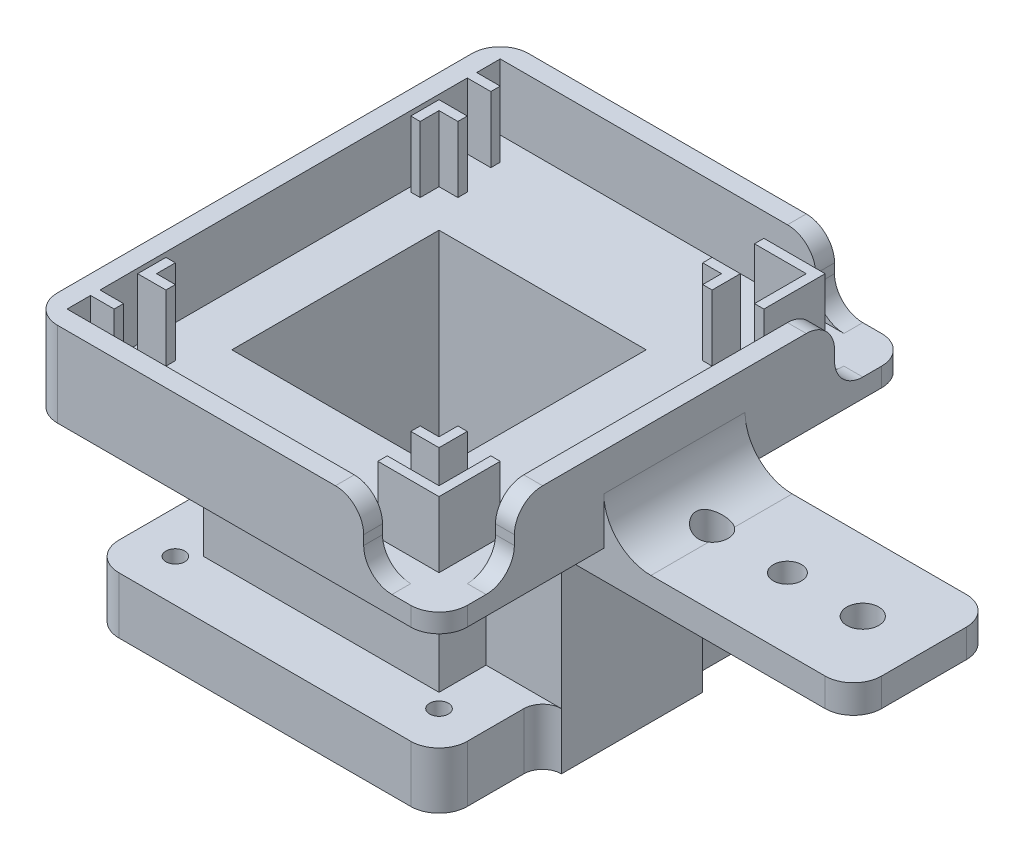
SolidWorks part; units mm, degrees
ref_plane "前视基准面" through (0, 0, 0) normal (0, 0, 1) x (1, 0, 0)
ref_plane "上视基准面" through (0, 0, 0) normal (0, 1, 0) x (1, 0, 0)
ref_plane "右视基准面" through (0, 0, 0) normal (1, 0, 0) x (0, 0, -1)
sketch "草图2" plane through (0, 0, 0) normal (0, 1, 0) x (1, 0, 0)
  line L1 (18.5, -18.5) -> (-18.5, -18.5)
  line L2 (18.5, -18.5) -> (18.5, 18.5)
  line L3 (18.5, 18.5) -> (-18.5, 18.5)
  line L4 (-18.5, -18.5) -> (-18.5, 18.5)
  line L5 (18.5, -18.5) -> (-18.5, 18.5) construction
  line L6 (18.5, 18.5) -> (-18.5, -18.5) construction
  point P0 (0, 0)
  dimension "D1" = 37
  dimension "D2" = 37
extrude "凸台-拉伸1" add sketch "草图2" along normal blind 23
sketch "草图3" plane through (0, 0, 0) normal (0, -1, 0) x (1, 0, 0)
  line L1 (11, -11) -> (-11, -11)
  line L2 (11, -11) -> (11, 11)
  line L3 (11, 11) -> (-11, 11)
  line L4 (-11, -11) -> (-11, 11)
  line L5 (11, -11) -> (-11, 11) construction
  line L6 (11, 11) -> (-11, -11) construction
  point P1 (0, 0)
  dimension "D1" = 22
  dimension "D2" = 22
extrude "切除-拉伸1" cut sketch "草图3" against normal blind 23
sketch3d "3D草图1" plane through (0, 0, 0) normal (0, 0, 1) x (1, 0, 0)
  dimension "D1" = 6
sketch "草图19" plane through (0, 6, 0) normal (0, -1, 0) x (-1, 0, 0)
  line L1 (-12.5, -12.5) -> (12.5, -12.5)
  line L2 (-12.5, -12.5) -> (-12.5, 12.5)
  line L3 (-12.5, 12.5) -> (12.5, 12.5)
  line L4 (12.5, -12.5) -> (12.5, 12.5)
  line L5 (-12.5, -12.5) -> (12.5, 12.5) construction
  line L6 (-12.5, 12.5) -> (12.5, -12.5) construction
  point P0 (0, 0)
  dimension "D1" = 25
  dimension "D2" = 25
extrude "切除-拉伸17" cut sketch "草图19" against normal blind 17 flip side to cut
sketch "草图4" plane through (0, 23, 0) normal (0, 1, 0) x (1, 0, 0)
  line L1 (25, 25) -> (-25, 25)
  line L2 (25, 25) -> (25, -25)
  line L3 (25, -25) -> (-25, -25)
  line L4 (-25, 25) -> (-25, -25)
  line L5 (25, 25) -> (-25, -25) construction
  line L6 (25, -25) -> (-25, 25) construction
  point P0 (0, 0)
  dimension "D1" = 50
  dimension "D2" = 50
extrude "凸台-拉伸2" add sketch "草图4" along normal blind 9
sketch "草图5" plane through (0, 32, 0) normal (0, 1, 0) x (1, 0, 0)
  line L1 (23, 23) -> (-23, 23)
  line L2 (23, 23) -> (23, -23)
  line L3 (23, -23) -> (-23, -23)
  line L4 (-23, 23) -> (-23, -23)
  line L5 (23, 23) -> (-23, -23) construction
  line L6 (23, -23) -> (-23, 23) construction
  point P0 (0, 0)
  dimension "D1" = 46
  dimension "D2" = 46
extrude "切除-拉伸3" cut sketch "草图5" against normal blind 7
sketch "草图12" plane through (0, 25, 0) normal (0, 1, 0) x (1, 0, 0)
  line L0 (-25, 25) -> (-25, -25) construction
  line L1 (-17, -17) -> (-25, -17)
  line L2 (-17, -17) -> (-17, -25)
  line L3 (-17, -25) -> (-25, -25)
  line L4 (-25, -17) -> (-25, -25)
  line L5 (-25, -25) -> (25, -25) construction
  line L6 (-17, 17) -> (-25, 17)
  line L7 (-17, 17) -> (-17, 25)
  line L8 (-17, 25) -> (-25, 25)
  line L9 (-25, 17) -> (-25, 25)
  line L10 (17, 17) -> (17, 25)
  line L11 (17, 17) -> (25, 17)
  line L12 (25, 17) -> (25, 25)
  line L13 (17, 25) -> (25, 25)
  line L14 (17, -17) -> (25, -17)
  line L15 (17, -17) -> (17, -25)
  line L16 (17, -25) -> (25, -25)
  line L17 (25, -17) -> (25, -25)
  dimension "D1" = 0
  dimension "D2" = 0
  dimension "D3" = 8
  dimension "D4" = 8
  dimension "D5" = 4
extrude "切除-拉伸14" cut sketch "草图12" along normal blind 14
sketch "草图6" plane through (0, 25, 0) normal (0, 1, 0) x (1, 0, 0)
  line L1 (11, 11) -> (-11, 11)
  line L2 (11, 11) -> (11, -11)
  line L3 (11, -11) -> (-11, -11)
  line L4 (-11, 11) -> (-11, -11)
  line L5 (11, 11) -> (-11, -11) construction
  line L6 (11, -11) -> (-11, 11) construction
  point P0 (0, 0)
  dimension "D1" = 22
  dimension "D2" = 22
extrude "切除-拉伸4" cut sketch "草图6" against normal blind 2
sketch "草图11" plane through (0, 0, 0) normal (0, -1, 0) x (1, 0, 0)
  line L0 (18.5, 18.5) -> (18.5, -18.5) construction
  line L1 (-18.5, 18.5) -> (18.5, 18.5) construction
  circle A0 centre (14, 14) radius 1
  circle A1 centre (14, -14) radius 1
  circle A2 centre (-14, -14) radius 1
  circle A3 centre (-14, 14) radius 1
  dimension "D1" = 4.5
  dimension "D3" = 2
  dimension "D2" = 4.5
  dimension "D4" = 4
extrude "切除-拉伸7" cut sketch "草图11" against normal blind 8
sketch "草图13" plane through (0, 25, 0) normal (0, 1, 0) x (1, 0, 0)
  line L1 (-20.5, 20.5) -> (20.5, 20.5)
  line L2 (-20.5, 20.5) -> (-20.5, -20.5)
  line L3 (-20.5, -20.5) -> (20.5, -20.5)
  line L4 (20.5, 20.5) -> (20.5, -20.5)
  line L5 (-20.5, 20.5) -> (20.5, -20.5) construction
  line L6 (-20.5, -20.5) -> (20.5, 20.5) construction
  line L7 (-19.5, 19.5) -> (19.5, 19.5)
  line L8 (-19.5, 19.5) -> (-19.5, -19.5)
  line L9 (-19.5, -19.5) -> (19.5, -19.5)
  line L10 (19.5, 19.5) -> (19.5, -19.5)
  line L11 (-19.5, 19.5) -> (19.5, -19.5) construction
  line L12 (-19.5, -19.5) -> (19.5, 19.5) construction
  point P0 (0, 0)
  point P6 (0, 0)
  dimension "D1" = 41
  dimension "D2" = 41
  dimension "D3" = 39
  dimension "D4" = 39
extrude "凸台-拉伸3" add sketch "草图13" along normal blind 7
sketch "草图17" plane through (0, 25, 0) normal (0, 1, 0) x (1, 0, 0)
  line L1 (15, -15) -> (-15, -15)
  line L2 (15, -15) -> (15, 15)
  line L3 (15, 15) -> (-15, 15)
  line L4 (-15, -15) -> (-15, 15)
  line L5 (15, -15) -> (-15, 15) construction
  line L6 (15, 15) -> (-15, -15) construction
  line L7 (16, -16) -> (-16, -16)
  line L8 (16, -16) -> (16, 16)
  line L9 (16, 16) -> (-16, 16)
  line L10 (-16, -16) -> (-16, 16)
  line L11 (16, -16) -> (-16, 16) construction
  line L12 (16, 16) -> (-16, -16) construction
  point P0 (0, 0)
  point P6 (0, 0)
  dimension "D1" = 30
  dimension "D2" = 30
  dimension "D3" = 32
  dimension "D4" = 32
extrude "凸台-拉伸4" add sketch "草图17" along normal blind 7
sketch "草图15" plane through (0, 25, 0) normal (0, 1, 0) x (1, 0, 0)
  line L0 (-14, -19.5) -> (-14, -20.5)
  line L1 (19.5, 14) -> (20.5, 14)
  line L2 (19.5, 14) -> (19.5, -14)
  line L3 (19.5, -14) -> (20.5, -14)
  line L4 (20.5, 14) -> (20.5, -14)
  line L5 (19.5, 14) -> (20.5, -14) construction
  line L6 (19.5, -14) -> (20.5, 14) construction
  line L7 (20.5, -20.5) -> (20.5, 20.5) construction
  line L8 (14, -20.5) -> (-14, -20.5)
  line L9 (19.5, -19.5) -> (19.5, 19.5) construction
  line L10 (14, -19.5) -> (-14, -19.5)
  line L11 (14, -19.5) -> (14, -20.5)
  line L12 (-19.5, 14) -> (-20.5, 14)
  line L13 (-20.5, -14) -> (-20.5, 14)
  line L14 (-19.5, -14) -> (-19.5, 14)
  line L15 (-19.5, -14) -> (-20.5, -14)
  line L16 (14, 19.5) -> (14, 20.5)
  line L17 (-14, 20.5) -> (14, 20.5)
  line L18 (-14, 19.5) -> (14, 19.5)
  line L19 (-14, 19.5) -> (-14, 20.5)
  point P0 (20, 0)
  point P5 (20.5, 0)
  point P6 (19.5, 0)
  point P11 (19.5, 0)
  dimension "D1" = 0
  dimension "D2" = 1
  dimension "D3" = 0
  dimension "D4" = 28
  dimension "D5" = 4
extrude "切除-拉伸15" cut sketch "草图15" along normal blind 7
sketch "草图18" plane through (0, 25, 0) normal (0, 1, 0) x (1, 0, 0)
  line L0 (15, -15) -> (15, 15) construction
  line L1 (16, -13) -> (15, -13)
  line L2 (16, -13) -> (16, 13)
  line L3 (16, 13) -> (15, 13)
  line L4 (15, -13) -> (15, 13)
  line L5 (16, -13) -> (15, 13) construction
  line L6 (16, 13) -> (15, -13) construction
  line L7 (16, -16) -> (16, 16) construction
  line L32 (-13, -16) -> (13, -16)
  line L33 (13, -16) -> (13, -15)
  line L34 (-13, -15) -> (13, -15)
  line L35 (-13, -16) -> (-13, -15)
  line L36 (-16, 13) -> (-16, -13)
  line L37 (-16, -13) -> (-15, -13)
  line L38 (-15, 13) -> (-15, -13)
  line L39 (-16, 13) -> (-15, 13)
  line L40 (13, 16) -> (-13, 16)
  line L41 (-13, 16) -> (-13, 15)
  line L42 (13, 15) -> (-13, 15)
  line L43 (13, 16) -> (13, 15)
  line L44 (0, 0) -> (15, -13) construction
  point P0 (15.5, 0)
  point P7 (16, 0)
  point P10 (16, 0)
  dimension "D1" = 0
  dimension "D2" = 1
  dimension "D3" = 0
  dimension "D4" = 26
  dimension "D5" = 4
  dimension "D6" = 19.8494
extrude "切除-拉伸16" cut sketch "草图18" along normal blind 7
sketch "草图20" plane through (0, 0, 0) normal (0, -1, 0) x (1, 0, 0)
  line L0 (-11, -11) -> (11, -11) construction
  line L1 (11, 0) -> (14, 0)
  line L2 (11, 0) -> (11, -10.5)
  line L3 (11, -10.5) -> (14, -10.5)
  line L4 (14, 0) -> (14, -10.5)
  line L5 (11, 0) -> (14, -10.5) construction
  line L6 (11, -10.5) -> (14, 0) construction
  line L7 (11, -11) -> (11, 11) construction
  point P0 (12.5, -5.25)
  dimension "D1" = 0.5
  dimension "D2" = 0
  dimension "D3" = 3
  dimension "D4" = 10.5
extrude "切除-拉伸18" cut sketch "草图20" against normal blind 3.5
sketch "草图21" plane through (0, 0, 0) normal (0, -1, 0) x (1, 0, 0)
  line L0 (-11, -11) -> (11, -11) construction
  line L1 (-11, -7) -> (-15.5, -7)
  line L2 (-11, -7) -> (-11, 3)
  line L3 (-11, 3) -> (-15.5, 3)
  line L4 (-15.5, -7) -> (-15.5, 3)
  line L5 (-11, -7) -> (-15.5, 3) construction
  line L6 (-11, 3) -> (-15.5, -7) construction
  line L7 (-11, 11) -> (-11, -11) construction
  point P0 (-13.25, -2)
  dimension "D1" = 4
  dimension "D2" = 10
  dimension "D3" = 0
  dimension "D4" = 4.5
extrude "切除-拉伸19" cut sketch "草图21" against normal blind 1
sketch "草图22" plane through (0, 0, 0) normal (0, -1, 0) x (1, 0, 0)
  line L1 (-2.5, -11) -> (2.5, -11)
  line L2 (-2.5, -11) -> (-2.5, -12)
  line L3 (-2.5, -12) -> (2.5, -12)
  line L4 (2.5, -11) -> (2.5, -12)
  line L5 (-2.5, -11) -> (2.5, -12) construction
  line L6 (-2.5, -12) -> (2.5, -11) construction
  line L7 (-11, -11) -> (11, -11) construction
  line L11 (0, 0) -> (7.3651, 0) construction
  line L13 (-2.5, 12) -> (2.5, 12)
  line L14 (2.5, 11) -> (2.5, 12)
  line L15 (-2.5, 11) -> (2.5, 11)
  line L16 (-2.5, 11) -> (-2.5, 12)
  point P0 (0, -11.5)
  point P7 (0, -11)
  point P8 (0, -11)
  point P9 (-2.5, -11.5)
  dimension "D1" = 1
  dimension "D2" = 0
  dimension "D3" = 0
  dimension "D4" = 5
extrude "切除-拉伸21" cut sketch "草图22" against normal blind 7
sketch "草图24" plane through (0, 0, 0) normal (0, -1, 0) x (1, 0, 0)
  line L0 (-11, -11) -> (-2.5, -11) construction
  line L1 (-1.5, -11) -> (-7.5, -11)
  line L2 (-1.5, -11) -> (-1.5, -15.5)
  line L3 (-1.5, -15.5) -> (-7.5, -15.5)
  line L4 (-7.5, -11) -> (-7.5, -15.5)
  line L5 (-1.5, -11) -> (-7.5, -15.5) construction
  line L6 (-1.5, -15.5) -> (-7.5, -11) construction
  line L7 (-11, -7) -> (-11, -11) construction
  point P0 (-4.5, -13.25)
  dimension "D1" = 0
  dimension "D2" = 3.5
  dimension "D3" = 4.5
  dimension "D4" = 6
extrude "切除-拉伸22" cut sketch "草图24" against normal blind 1
sketch "草图25" plane through (0, 6, 0) normal (0, 1, 0) x (1, 0, 0)
  line L0 (18.5, 18.5) -> (18.5, -18.5) construction
  line L1 (18.5, 7.5) -> (12.5, 7.5)
  line L2 (18.5, 7.5) -> (18.5, -7.5)
  line L3 (18.5, -7.5) -> (12.5, -7.5)
  line L4 (12.5, 7.5) -> (12.5, -7.5)
  line L5 (18.5, 7.5) -> (12.5, -7.5) construction
  line L6 (18.5, -7.5) -> (12.5, 7.5) construction
  line L7 (12.5, 12.5) -> (12.5, -12.5) construction
  point P0 (15.5, 0)
  point P9 (15.5, -7.5)
  point P10 (18.5, 0)
  point P11 (18.5, 0)
  dimension "D1" = 0
  dimension "D2" = 0
  dimension "D3" = 15
  dimension "D4" = 0
extrude "凸台-拉伸5" add sketch "草图25" along normal blind 17
sketch "草图26" plane through (18.5, 0, 0) normal (1, 0, 0) x (0, 0, -1)
  line L0 (-7.5, 23) -> (7.5, 23) construction
  line L1 (7.5, 20) -> (-7.5, 20)
  line L2 (7.5, 20) -> (7.5, 23)
  line L3 (7.5, 23) -> (-7.5, 23)
  line L4 (-7.5, 20) -> (-7.5, 23)
  line L5 (7.5, 20) -> (-7.5, 23) construction
  line L6 (7.5, 23) -> (-7.5, 20) construction
  line L7 (7.5, 23) -> (7.5, 6) construction
  line L8 (-7.5, 23) -> (-7.5, 6) construction
  point P0 (0, 21.5)
  dimension "D1" = 0
  dimension "D2" = 0
  dimension "D3" = 0
  dimension "D4" = 3
extrude "凸台-拉伸6" add sketch "草图26" along normal blind 33
sketch "草图28" plane through (0, 23, 0) normal (0, -1, 0) x (1, 0, 0)
  line L0 (-25, 25) -> (25, 25) construction
  line L1 (-25, -25) -> (-18.5, -25)
  line L2 (-25, -25) -> (-25, 25)
  line L3 (-25, 25) -> (-18.5, 25)
  line L4 (-18.5, -25) -> (-18.5, 25)
  dimension "D1" = 0
  dimension "D2" = 6.5
extrude "切除-拉伸27" cut sketch "草图28" against normal blind 13
sketch "草图32" plane through (0, 23, 0) normal (0, -1, 0) x (1, 0, 0)
  line L0 (-18.5, 25) -> (25, 25) construction
  line L1 (-18.5, -25) -> (-16.5, -25)
  line L2 (-18.5, -25) -> (-18.5, 25)
  line L3 (-18.5, 25) -> (-16.5, 25)
  line L4 (-16.5, -25) -> (-16.5, 25)
  dimension "D1" = 2
extrude "凸台-拉伸9" add sketch "草图32" against normal blind 9
fillet "圆角5" radius 3 1 edges at (25, 24, -25) type face fillet first side face at (25, 25.6, 0) second side face at (7.8333, 26.6667, -25)
fillet "圆角6" radius 3 1 edges at (25, 24, 25) type face fillet first side face at (7.8333, 26.6667, 25) second side face at (25, 25.6, 0.6)
fillet "圆角7" radius 3 1 edges at (-18.5, 27.5, -25) type face fillet first side face at (-18.5, 27.5, 0) second side face at (6.8333, 26.6667, -25)
fillet "圆角8" radius 3 1 edges at (-18.5, 27.5, 25) type face fillet first side face at (-18.5, 27.5, 1.5) second side face at (6.8333, 26.6667, 25)
fillet "圆角9" radius 3 1 edges at (17, 32, -24) type face fillet first side face at (-8.6801, 32, 0) second side face at (17, 28.5, -24)
fillet "圆角10" radius 3 1 edges at (17, 25, -24) type face fillet first side face at (-14.6667, 25, 14.6667) second side face at (17, 27, -24)
fillet "圆角11" radius 3 1 edges at (24, 32, -17) type face fillet first side face at (24, 28.5, -17) second side face at (24, 32, 0)
fillet "圆角12" radius 3 1 edges at (24, 25, -17) type face fillet first side face at (24, 27, -17) second side face at (-14.6667, 25, 14.6667)
fillet "圆角13" radius 3 1 edges at (17, 32, 24) type face fillet first side face at (-9.0135, 32, 0) second side face at (17, 28.5, 24)
fillet "圆角14" radius 3 1 edges at (17, 25, 24) type face fillet first side face at (17, 27, 24) second side face at (-14.6667, 25, 14.6667)
fillet "圆角15" radius 3 1 edges at (24, 32, 17) type face fillet first side face at (24, 32, 1.5) second side face at (24, 28.5, 17)
fillet "圆角16" radius 3 1 edges at (24, 25, 17) type face fillet first side face at (24, 27, 17) second side face at (-14.6667, 25, 14.6667)
fillet "圆角17" radius 5 1 edges at (25, 23, 0) type face fillet first side face at (25, 26.4286, 0) second side face at (38.25, 23, 0)
fillet "圆角19" radius 3 1 edges at (-18.5, 3, -18.5) type face fillet first side face at (-18.5, 3, 0) second side face at (0, 3, -18.5)
fillet "圆角20" radius 3 1 edges at (-18.5, 3, 18.5) type face fillet first side face at (-18.5, 3, 1.5) second side face at (0, 3, 18.5)
fillet "圆角21" radius 3 1 edges at (18.5, 3, 18.5) type face fillet first side face at (18.5, 8, 0) second side face at (1.5, 3, 18.5)
fillet "圆角22" radius 3 1 edges at (18.5, 3, -18.5) type face fillet first side face at (18.5, 8, -0.75) second side face at (1.5, 3, -18.5)
sketch "草图34" plane through (18.5, 0, 0) normal (1, 0, 0) x (0, 0, -1)
  line L0 (7.5, 20) -> (7.5, 6) construction
  line L1 (-7.5, 20) -> (7.5, 20)
  line L2 (-7.5, 20) -> (-7.5, 0)
  line L3 (-7.5, 0) -> (7.5, 0)
  line L4 (7.5, 20) -> (7.5, 0)
  dimension "D1" = 20
extrude "凸台-拉伸10" add sketch "草图34" along normal blind 2
sketch "草图33" plane through (0, 20, 0) normal (0, -1, 0) x (1, 0, 0)
  line L0 (18.5, 7.5) -> (18.5, -7.5) construction
  line L1 (18.5, 0) -> (51.7925, 0) construction
  line L2 (37, 0) -> (37, 4.4072) construction
  line L3 (20.5, -7.5) -> (20.5, 7.5) construction
  circle A1 centre (29, 0) radius 1.7
  circle A2 centre (37, 0) radius 1.5
  circle A3 centre (45, 0) radius 1.7
  dimension "D2" = 3.4
  dimension "D4" = 3
  dimension "D1" = 8.5
  dimension "D3" = 8
extrude "切除-拉伸28" cut sketch "草图33" against normal blind 7
fillet "圆角23" radius 3 1 edges at (51.5, 21.5, 7.5) type face fillet first side face at (51.5, 21.5, 0) second side face at (25.9059, 15.5422, 7.5)
fillet "圆角24" radius 3 1 edges at (51.5, 21.5, -7.5) type face fillet first side face at (51.5, 21.5, -1.5) second side face at (25.9059, 15.5422, -7.5)
fillet "圆角25" radius 2 1 edges at (18.5, 3, 7.5) type face fillet first side face at (18.5, 3, 11.5) second side face at (25.3604, 15.5422, 7.5)
fillet "圆角26" radius 2 1 edges at (18.5, 3, -7.5) type face fillet first side face at (18.5, 3, -11.5) second side face at (25.3604, 15.5422, -7.5)
